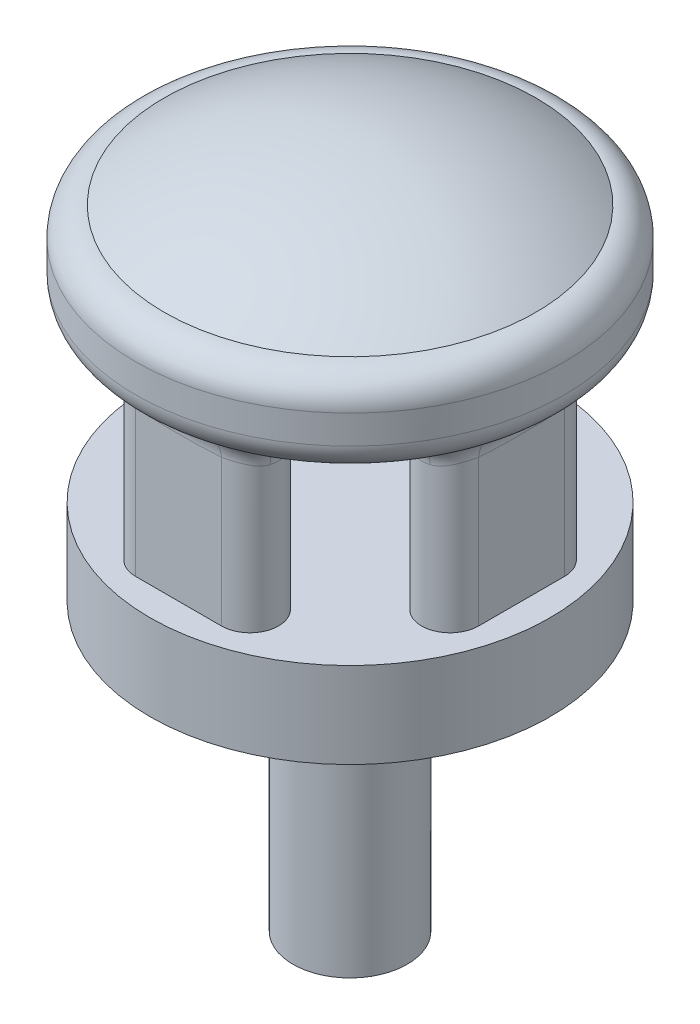
SolidWorks part; units mm, degrees
ref_plane "Front Plane" through (0, 0, 0) normal (0, 0, 1) x (1, 0, 0)
ref_plane "Top Plane" through (0, 0, 0) normal (0, 1, 0) x (1, 0, 0)
ref_plane "Right Plane" through (0, 0, 0) normal (1, 0, 0) x (0, 0, -1)
sketch "Sketch1" plane through (0, 0, 0) normal (0, 1, 0) x (1, 0, 0)
  circle A0 centre (0, 0) radius 9.525
  dimension "D1" = 19.05
extrude "button top" add sketch "Sketch1" along normal blind 3.81
sketch "Sketch2" plane through (0, 0, 0) normal (0, -1, 0) x (1, 0, 0)
  line L9 (-1.905, 6.35) -> (1.905, 6.35) construction
  line L10 (-1.905, 7.62) -> (1.905, 7.62)
  line L11 (-1.905, 5.08) -> (1.905, 5.08)
  arc A6 (-1.905, 7.62) -> (-1.905, 5.08) centre (-1.905, 6.35) ccw
  arc A7 (1.905, 5.08) -> (1.905, 7.62) centre (1.905, 6.35) ccw
  point P22 (0, 6.35)
  dimension "D2" = 1.27
  dimension "D1" = 6.35
  dimension "D8" = 3.81
extrude "connecting leg" add sketch "Sketch2" along normal blind 7.62
ref_axis "central axis" through (0, 3.81, 0) along (0, -1, 0)
pattern_circular "moar legs" count 4 over 360 about axis through (0, 3.81, 0) along (0, -1, 0) of "connecting leg"
ref_plane "base plane" through (0, -7.62, 0) normal (0, -1, 0) x (-1, 0, 0)
sketch "Sketch3" plane through (0, -7.62, 0) normal (0, -1, 0) x (-1, 0, 0)
  circle A0 centre (0, 0) radius 8.89
extrude "base" add sketch "Sketch3" along normal blind 3.81 separate body
fillet "Fillet2" radius 1.27 2 edges at (0, 3.81, 9.525) (0, 0, 9.525)
fillet "Fillet3" radius 1.27 16 edges at (0, 0, 5.08) (-3.175, 0, 6.35) (0, 0, 7.62) (3.175, 0, 6.35) (5.08, 0, 0) (6.35, 0, 3.175) (7.62, 0, 0) (6.35, 0, -3.175) (3.175, 0, -6.35) (0, 0, -7.62) (-3.175, 0, -6.35) (0, 0, -5.08) (-5.08, 0, 0) (-6.35, 0, -3.175) (-7.62, 0, 0) (-6.35, 0, 3.175)
dome "Dome1" faces to dome 1 distance 2.54 reverse direction no elliptical dome no face at (0, 3.81, 8.255) parameters "D1"=2.54
sketch "Sketch5" plane through (0, -11.43, 0) normal (0, -1, 0) x (1, 0, 0)
  circle A0 centre (0, 0) radius 2.54
extrude "Boss-Extrude2" add sketch "Sketch5" along normal blind 12.7
fillet "Fillet4" radius 2.54 1 edges at (0, -11.43, -2.54)
